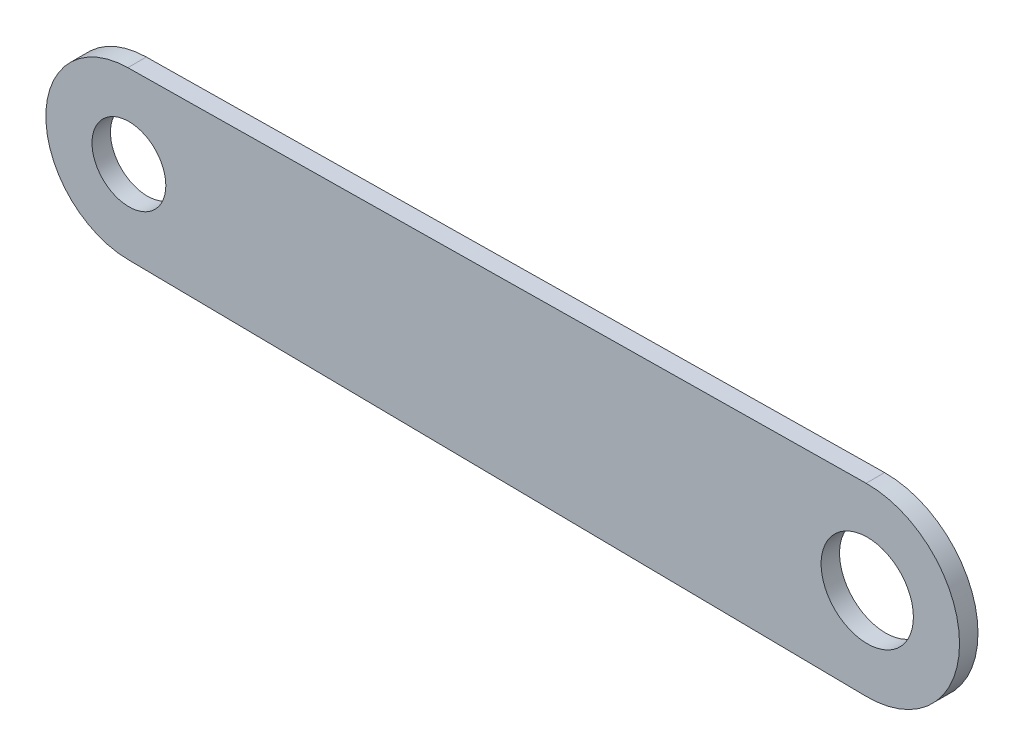
SolidWorks part; units mm, degrees
material "AISI 1020"
ref_plane "Спереди" through (0, 0, 0) normal (0, 0, 1) x (1, 0, 0)
ref_plane "Сверху" through (0, 0, 0) normal (0, 1, 0) x (1, 0, 0)
ref_plane "Справа" through (0, 0, 0) normal (1, 0, 0) x (0, 0, -1)
sketch "Эскиз2" plane through (0, 0, 0) normal (0, 0, 1) x (1, 0, 0)
  line L0 (-160.225, 17.9986) -> (-0.25, 19.9984)
  line L1 (-0.25, -19.9984) -> (-160.225, -17.9986)
  circle A0 centre (-160, 0) radius 8
  circle A1 centre (1046.0819, -364.6457) radius 8 construction
  circle A2 centre (0, 0) radius 10
  arc A3 (-160.225, 17.9986) -> (-160.225, -17.9986) centre (-160, 0) ccw
  arc A4 (-0.25, -19.9984) -> (-0.25, 19.9984) centre (0, 0) ccw
  dimension "D1" = 20
  dimension "D2" = 40
  dimension "D3" = 10
base flange "Базовая кромка1" sketch "Эскиз2" thickness 4 reverse thickness direction no parameters "D1"=0.74
sketch "Сгиб-Линии1" [suppressed] plane through (0, 0, 0) normal (0, 1, 0) x (1, 0, 0)
sketch "Граничная рамка1" [suppressed] plane through (0, 0, 0) normal (0, 1, 0) x (1, 0, 0)
sheet metal parameters "Листовой металл3" thickness 4 parameters "D1"=0.74
flat pattern "Развертка3" [suppressed]
sketch "Сгиб-Линии2" plane through (0, 0, 0) normal (0, 1, 0) x (1, 0, 0)
sketch3d "Граничная рамка2" [suppressed]
  line L0 (-17.7236, 22.2233, 0) -> (180.2484, 19.7484, 0) construction
  line L1 (-18.2236, -17.7736, 0) -> (179.7484, -20.2484, 0) construction
  line L2 (-17.7236, 22.2233, 0) -> (-18.2236, -17.7736, 0) construction
  line L3 (180.2484, 19.7484, 0) -> (179.7484, -20.2484, 0) construction
